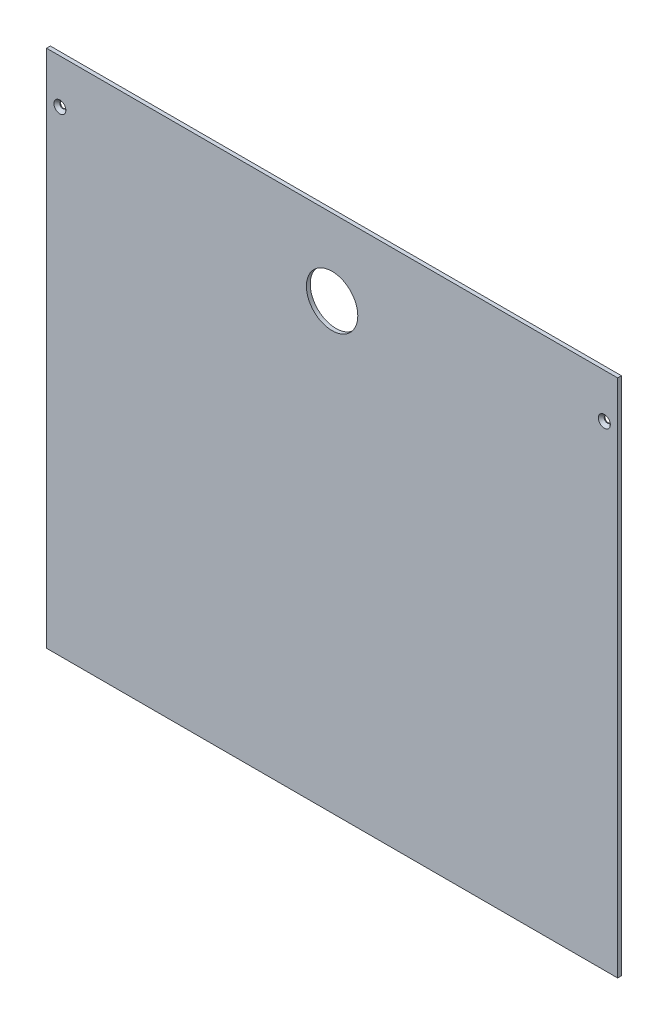
SolidWorks part; units mm, degrees
ref_plane "Front Plane" through (0, 0, 0) normal (0, 0, 1) x (1, 0, 0)
ref_plane "Top Plane" through (0, 0, 0) normal (0, 1, 0) x (1, 0, 0)
ref_plane "Right Plane" through (0, 0, 0) normal (1, 0, 0) x (0, 0, -1)
sketch "Sketch1" plane through (0, 0, 0) normal (0, 0, 1) x (1, 0, 0)
  line L0 (-137.45, 0) -> (-137.45, 300) construction
  line L1 (0, 0) -> (-300, 0)
  line L2 (0, 0) -> (0, 273)
  line L3 (0, 273) -> (-300, 273)
  line L4 (-300, 0) -> (-300, 273)
  dimension "D1" = 273
  dimension "D2" = 300
base flange "Base-Flange1" sketch "Sketch1" thickness 2 reverse thickness direction no parameters "D1"=2
ref_plane "Plane1" through (-150, 0, 0) normal (-1, 0, 0) x (0, 0, 1)
hole_wizard "CSK for M3 Oval Head Machine Screw1" positions "Sketch7" profile "Sketch8" countersink size "M3" standard "ANSI Metric" end condition through all
sketch "Sketch7" plane through (0, 0, 0) normal (0, 0, 1) x (1, 0, 0)
  line L0 (-300, 273) -> (-300, 0) construction
  line L1 (0, 273) -> (-300, 273) construction
  point P0 (-293, 249.78)
  dimension "D1" = 7
  dimension "D2" = 23.22
sketch "Sketch8" plane through (-293, 249.78, 0) normal (1, 0, 0) x (0, -1, 0)
  line L0 (0, 0) -> (0, 2)
  line L1 (0, 2) -> (1.6, 2)
  line L2 (1.6, 2) -> (1.6, 1.55)
  line L3 (1.6, 1.55) -> (3.15, 0)
  line L5 (3.15, 0) -> (0, 0)
  line L6 (-1.6, 1.55) -> (-3.15, 0) construction
  line L11 (0, -6.35) -> (0, 107.95) construction
  dimension "Thru Hole Dia." = 3.2
  dimension "Thru Hole Depth" = 2
  dimension "Near C'Sink Dia." = 6.3
  dimension "Near C'Sink Angle" = 90
mirror "Mirror1" about plane through (-150, 0, 0) normal (-1, 0, 0) of "CSK for M3 Oval Head Machine Screw1"
hole_wizard "M25 Clearance Hole1" positions "Sketch10" profile "Sketch9" hole size "M25" standard "ANSI Metric" end condition through all
sketch "Sketch10" plane through (0, 0, 0) normal (0, 0, 1) x (1, 0, 0)
  line L0 (-150, 1.1) -> (-150, -1.1) construction
  line L1 (0, 273) -> (-300, 273) construction
  point P0 (-150, 233)
  dimension "D1" = 40
sketch "Sketch9" plane through (-150, 233, 0) normal (1, 0, 0) x (0, -1, 0)
  line L0 (0, 0) -> (0, 2)
  line L1 (0, 2) -> (13.5, 2)
  line L2 (13.5, 2) -> (13.5, 0)
  line L5 (13.5, 0) -> (0, 0)
  line L11 (0, -6.35) -> (0, 107.95) construction
  dimension "Thru Hole Dia." = 27
  dimension "Thru Hole Depth" = 2
sketch "Bend-Lines1" [suppressed] plane through (0, 0, 0) normal (0, 1, 0) x (1, 0, 0)
sketch "Bounding-Box1" [suppressed] plane through (0, 0, 0) normal (0, 1, 0) x (1, 0, 0)
sheet metal parameters "Sheet-Metal1" thickness 2 parameters "D1"=2
flat pattern "Flat-Pattern1" [suppressed]
sketch "Bend-Lines2" plane through (0, 0, 0) normal (0, 1, 0) x (1, 0, 0)
sketch3d "Bounding-Box2" [suppressed]
  line L0 (0, 300, 0) -> (0, 0, 0) construction
  line L1 (-274.9, 300, 0) -> (-274.9, 0, 0) construction
  line L2 (0, 300, 0) -> (-274.9, 300, 0) construction
  line L3 (0, 0, 0) -> (-274.9, 0, 0) construction
sheet metal parameters "Sheet-Metal2" thickness 2 parameters "D1"=2
flat pattern "Flat-Pattern1"
sketch "Bend-Lines2" plane through (0, 0, 0) normal (0, 1, 0) x (1, 0, 0)
sketch3d "Bounding-Box2" [suppressed]
  line L0 (0, 300, 0) -> (0, 0, 0) construction
  line L1 (-274.9, 300, 0) -> (-274.9, 0, 0) construction
  line L2 (0, 300, 0) -> (-274.9, 300, 0) construction
  line L3 (0, 0, 0) -> (-274.9, 0, 0) construction
sheet metal parameters "Sheet-Metal3" thickness 2 parameters "D1"=2
flat pattern "Flat-Pattern1"
sketch "Bend-Lines2" plane through (0, 0, 0) normal (0, 1, 0) x (1, 0, 0)
sketch3d "Bounding-Box2" [suppressed]
  line L0 (0, 300, 0) -> (0, 0, 0) construction
  line L1 (-274.9, 300, 0) -> (-274.9, 0, 0) construction
  line L2 (0, 300, 0) -> (-274.9, 300, 0) construction
  line L3 (0, 0, 0) -> (-274.9, 0, 0) construction
sheet metal parameters "Sheet-Metal4" thickness 2 parameters "D1"=2
flat pattern "Flat-Pattern1"
sketch "Bend-Lines2" plane through (0, 0, 0) normal (0, 1, 0) x (1, 0, 0)
sketch3d "Bounding-Box2" [suppressed]
  line L0 (-300, 0, 0) -> (0, 0, 0) construction
  line L1 (-300, 274, 0) -> (0, 274, 0) construction
  line L2 (-300, 0, 0) -> (-300, 274, 0) construction
  line L3 (0, 0, 0) -> (0, 274, 0) construction
equation "\"length_edge_flange\" = 33.11mm"
equation "\"distance_fente_rampe\" = 158.61mm"
equation "\"distance_interieur\" = 300mm"
equation "\"longeur_interieur\"= 274.9mm"
equation "\"distance_trou\" = 28.82mm"
